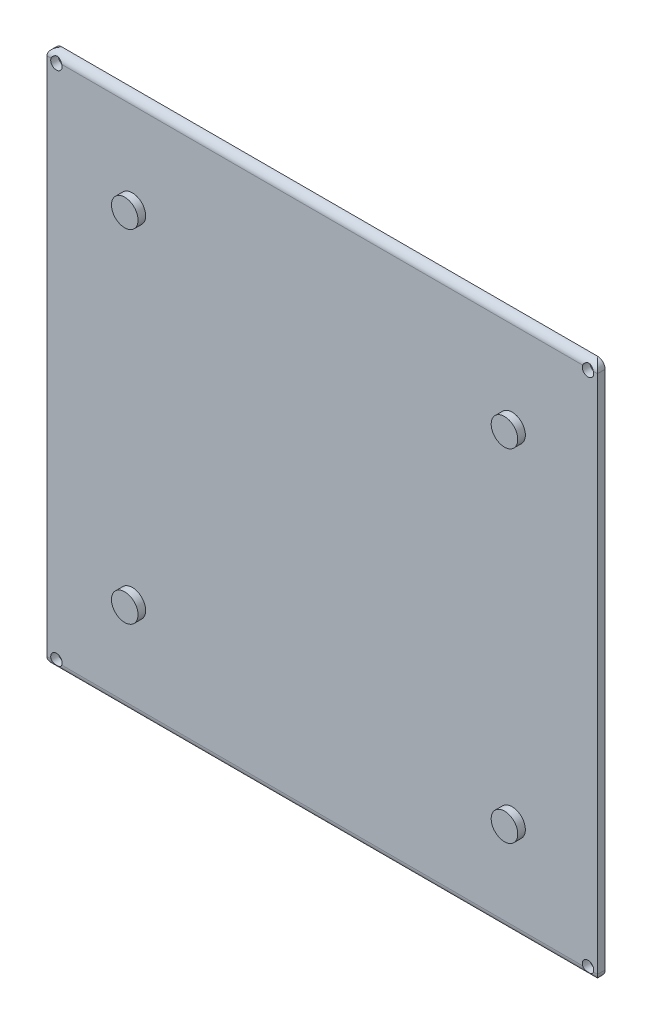
SolidWorks part; units mm, degrees
ref_plane "Front Plane" through (0, 0, 0) normal (0, 0, 1) x (1, 0, 0)
ref_plane "Top Plane" through (0, 0, 0) normal (0, 1, 0) x (1, 0, 0)
ref_plane "Right Plane" through (0, 0, 0) normal (1, 0, 0) x (0, 0, -1)
sketch "Sketch1" plane through (0, 0, 0) normal (0, 0, 1) x (1, 0, 0)
  line L1 (72.5, -70.5) -> (-72.5, -70.5)
  line L2 (72.5, -70.5) -> (72.5, 70.5)
  line L3 (72.5, 70.5) -> (-72.5, 70.5)
  line L4 (-72.5, -70.5) -> (-72.5, 70.5)
  line L5 (72.5, -70.5) -> (-72.5, 70.5) construction
  line L6 (72.5, 70.5) -> (-72.5, -70.5) construction
  point P0 (0, 0)
  dimension "D1" = 145
  dimension "D2" = 141
extrude "Boss-Extrude1" add sketch "Sketch1" along normal blind 2
sketch "Sketch2" plane through (0, 0, 2) normal (0, 0, 1) x (1, 0, 0)
  line L0 (72.5, 70.5) -> (-72.5, 70.5) construction
  line L1 (-72.5, 70.5) -> (-72.5, -70.5) construction
  line L2 (4.95, 0) -> (-4.95, 0) construction
  line L3 (0, -4.95) -> (0, 4.95) construction
  circle A0 centre (-70, 68) radius 1.5
  circle A1 centre (-70, -68) radius 1.5
  circle A2 centre (70, -68) radius 1.5
  circle A3 centre (70, 68) radius 1.5
  dimension "D1" = 3
  dimension "D2" = 2.5
  dimension "D3" = 2.5
extrude "Cut-Extrude1" cut sketch "Sketch2" against normal blind 5
fillet "Fillet1" radius 2 6 edges at (0, 70.5, 2) (0, -70.5, 2) (72.5, -70.5, 1) (-72.5, -70.5, 1) (72.5, 70.5, 1) (-72.5, 70.5, 1)
sketch "Sketch3" plane through (0, 0, 0) normal (0, 0, -1) x (-1, 0, 0)
  line L0 (4.95, 0) -> (-4.95, 0) construction
  line L5 (50, -43.5) -> (-50, 43.5) construction
  line L6 (50, 43.5) -> (-50, -43.5) construction
  line L7 (0, 4.95) -> (0, -4.95) construction
  circle A0 centre (-48, 41.5) radius 2.5
  circle A1 centre (-48, -41.5) radius 2.5
  circle A2 centre (48, -41.5) radius 2.5
  circle A3 centre (48, 41.5) radius 2.5
  point P0 (0, 0)
  dimension "D3" = 5
  dimension "D1" = 100
  dimension "D2" = 87
extrude "Boss-Extrude2" add sketch "Sketch3" along normal blind 5
fillet "Fillet2" radius 2 4 edges at (-45.5, -41.5, 0) (50.5, -41.5, 0) (-45.5, 41.5, 0) (50.5, 41.5, 0)
sketch "Sketch4" plane through (0, 0, -5) normal (0, 0, -1) x (-1, 0, 0)
  circle A0 centre (-48, 41.5) radius 1.5
  dimension "D1" = 3
extrude "Cut-Extrude2" cut sketch "Sketch4" against normal blind 3
mirror "Mirror1" about plane through (0, 0, 0) normal (1, 0, 0) of "Cut-Extrude2" second plane through (0, 0, 0) second plane normal (0, 1, 0)
sketch "Sketch5" plane through (0, 0, 2) normal (0, 0, 1) x (1, 0, 0)
  circle A0 centre (-50, 45) radius 3.5
  dimension "D1" = 7
  dimension "D2" = 45
  dimension "D3" = 50
extrude "Boss-Extrude3" add sketch "Sketch5" along normal blind 2
mirror "Mirror2" about plane through (0, 0, 0) normal (1, 0, 0) of "Boss-Extrude3" second plane through (0, 0, 0) second plane normal (0, 1, 0)
